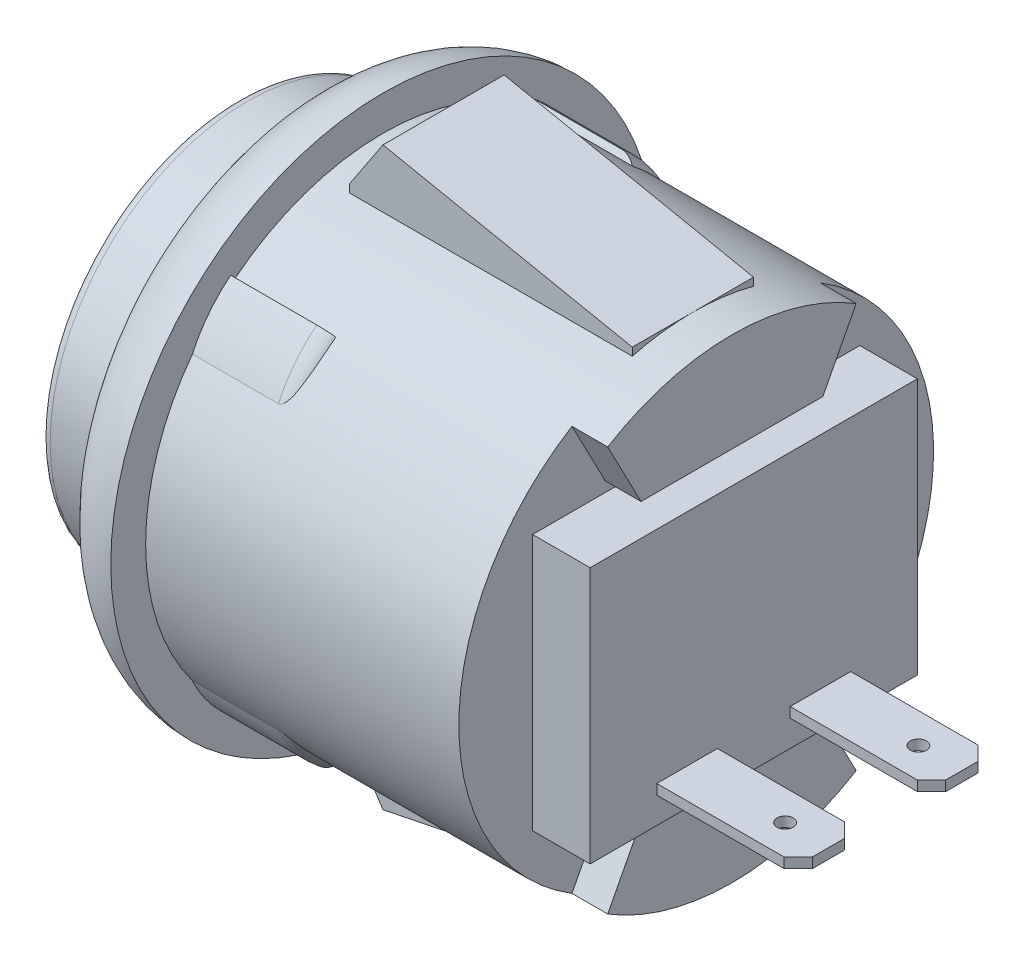
SolidWorks part; units mm, degrees
ref_plane "Front Plane" through (0, 0, 0) normal (0, 0, 1) x (1, 0, 0)
ref_plane "Top Plane" through (0, 0, 0) normal (0, 1, 0) x (1, 0, 0)
ref_plane "Right Plane" through (0, 0, 0) normal (1, 0, 0) x (0, 0, -1)
sketch "Sketch1" plane through (0, 0, 0) normal (0, 0, 1) x (1, 0, 0)
  line L0 (0, 0) -> (0, 9.75)
  line L1 (0, 9.75) -> (3.5, 9.75)
  line L2 (7.225, 13.475) -> (7.225, 11.75)
  line L3 (7.225, 11.75) -> (24.5, 11.75)
  line L4 (24.5, 11.75) -> (24.5, 0)
  line L5 (24.5, 0) -> (0, 0)
  line L6 (0, 0) -> (-7.0673, 0) construction
  line L7 (3.5, 9.75) -> (3.5, 8.8605) construction
  line L8 (7.225, 13.475) -> (8.6863, 13.475) construction
  arc A0 (7.225, 13.475) -> (3.5, 9.75) centre (7.225, 9.75) ccw
  dimension "D1" = 23.5
  dimension "D2" = 19.5
  dimension "D3" = 24.5
  dimension "D4" = 26.95
  dimension "D5" = 3.5
revolve "Revolve1" add sketch "Sketch1" angle 360 about L5
sketch "Sketch7" plane through (7.225, 0, 0) normal (1, 0, 0) x (0, 0, -1)
  line L0 (-7.3373, 9.1775) -> (-7.5402, 9.4314)
  line L1 (0, 0) -> (7.2137, 0) construction
  line L2 (0, 0) -> (0, 5.1375) construction
  line L3 (-7.3373, -9.1775) -> (-7.5402, -9.4314)
  line L4 (7.3373, -9.1775) -> (7.5402, -9.4314)
  line L5 (7.3373, 9.1775) -> (7.5402, 9.4314)
  circle A0 centre (0, 0) radius 12.075 construction
  circle A1 centre (0, 0) radius 11.75 construction
  arc A2 (-7.5402, 9.4314) -> (-9.4373, 7) centre (-3.3839, 4.2327) ccw
  arc A3 (-7.3373, 9.1775) -> (-9.4373, 7) centre (0, 0) ccw
  arc A4 (-7.5402, -9.4314) -> (-9.4373, -7) centre (-3.3839, -4.2327) cw
  arc A5 (-7.3373, -9.1775) -> (-9.4373, -7) centre (0, 0) cw
  arc A6 (7.3373, -9.1775) -> (9.4373, -7) centre (0, 0) ccw
  arc A7 (7.5402, -9.4314) -> (9.4373, -7) centre (3.3839, -4.2327) ccw
  arc A8 (7.5402, 9.4314) -> (9.4373, 7) centre (3.3839, 4.2327) cw
  arc A9 (7.3373, 9.1775) -> (9.4373, 7) centre (0, 0) cw
  dimension "D1" = 24.15
  dimension "D2" = 3
  dimension "D3" = 7
extrude "Boss-Extrude4" add sketch "Sketch7" along normal blind 5.26
fillet "Fillet2" radius 1 4 edges at (12.485, -8.3271, 8.6315) (12.485, -8.3271, -8.6315) (12.485, 8.3271, -8.6315) (12.485, 8.3271, 8.6315)
sketch "Sketch8" plane through (24.5, 0, 0) normal (1, 0, 0) x (0, 0, -1)
  line L0 (-6.15, 10.012) -> (-4.5, 6.85)
  line L1 (-4.5, 6.85) -> (4.5, 6.85)
  line L2 (4.5, 6.85) -> (6.15, 10.012)
  line L3 (0, 0) -> (9.6231, 0) construction
  line L4 (4.5, -6.85) -> (6.15, -10.012)
  line L5 (-4.5, -6.85) -> (4.5, -6.85)
  line L6 (-6.15, -10.012) -> (-4.5, -6.85)
  circle A0 centre (0, 0) radius 11.75 construction
  arc A1 (7.3373, 9.1775) -> (-7.3373, 9.1775) centre (0, 0) ccw construction
  arc A2 (6.15, 10.012) -> (-6.15, 10.012) centre (0, 0) ccw
  arc A3 (6.15, -10.012) -> (-6.15, -10.012) centre (0, 0) cw
  point P4 (0, 6.85)
  dimension "D1" = 12.3
  dimension "D2" = 9
  dimension "D3" = 6.85
extrude "Cut-Extrude2" cut sketch "Sketch8" against normal blind 1.77 flip side to cut
sketch "Sketch2" plane through (22.73, 0, 0) normal (1, 0, 0) x (0, 0, -1)
  line L1 (-8.1, 6.35) -> (8.1, 6.35)
  line L2 (-8.1, 6.35) -> (-8.1, -6.35)
  line L3 (-8.1, -6.35) -> (8.1, -6.35)
  line L4 (8.1, 6.35) -> (8.1, -6.35)
  line L5 (-8.1, 6.35) -> (8.1, -6.35) construction
  line L6 (-8.1, -6.35) -> (8.1, 6.35) construction
  point P0 (0, 0)
  dimension "D1" = 16.2
  dimension "D2" = 12.7
extrude "Boss-Extrude1" add sketch "Sketch2" along normal blind 2.85
sketch "Sketch3" plane through (25.58, 0, 0) normal (1, 0, 0) x (0, 0, -1)
  line L0 (0, 0) -> (0, -4.1104) construction
  line L1 (-4.8, -5.05) -> (-4.8, -4.55)
  line L2 (-4.8, -5.05) -> (-1.8, -5.05)
  line L3 (-1.8, -5.05) -> (-1.8, -4.55)
  line L4 (-4.8, -4.55) -> (-1.8, -4.55)
  line L5 (1.8, -5.05) -> (1.8, -4.55)
  line L6 (1.8, -5.05) -> (4.8, -5.05)
  line L7 (4.8, -5.05) -> (4.8, -4.55)
  line L8 (1.8, -4.55) -> (4.8, -4.55)
  line L9 (-8.1, -6.35) -> (8.1, -6.35) construction
  dimension "D1" = 0.5
  dimension "D2" = 3
  dimension "D3" = 3.6
  dimension "D4" = 1.3
extrude "Boss-Extrude2" add sketch "Sketch3" along normal blind 7
sketch "Sketch4" plane through (0, -4.55, 0) normal (0, 1, 0) x (-1, 0, 0)
  line L0 (-32.58, 1.8) -> (-32.58, 4.8) construction
  line L1 (-32.58, -4.8) -> (-32.58, -1.8) construction
  circle A0 centre (-30.43, 3.3) radius 0.4
  circle A1 centre (-30.43, -3.3) radius 0.4
  point P8 (-32.58, 3.3)
  point P12 (-32.58, -3.3)
  dimension "D1" = 0.8
  dimension "D2" = 2.15
extrude "Cut-Extrude1" cut sketch "Sketch4" against normal through all
chamfer "Chamfer1" distance 0.7 angle 45 4 edges at (32.58, -4.8, -4.8) (32.58, -4.8, -1.8) (32.58, -4.8, 1.8) (32.58, -4.8, 4.8)
sketch "Sketch5" plane through (0, 0, 0) normal (0, 0, 1) x (1, 0, 0)
  line L0 (22.5667, -11.75) -> (10.225, -14.25)
  line L2 (10.225, -14.25) -> (8.5667, -11.75)
  line L4 (0, 0) -> (-5.0022, 0) construction
  line L5 (8.5667, 10.75) -> (8.5667, 11.75)
  line L6 (22.5667, 10.75) -> (8.5667, 10.75)
  line L7 (22.5667, -11.75) -> (22.5667, -10.75)
  line L8 (22.5667, -10.75) -> (8.5667, -10.75)
  line L9 (8.5667, -10.75) -> (8.5667, -11.75)
  line L10 (7.225, -13.475) -> (7.225, 13.475) construction
  line L11 (22.5667, 11.75) -> (22.5667, 10.75)
  line L12 (10.225, 14.25) -> (8.5667, 11.75)
  line L13 (22.5667, 11.75) -> (10.225, 14.25)
  line L14 (7.225, -11.75) -> (24.5, -11.75)
  line L15 (24.5, 11.75) -> (7.225, 11.75)
  line L17 (7.225, -11.75) -> (24.5, -11.75) construction
  dimension "D1" = 2.5
  dimension "D2" = 14
  dimension "D3" = 3
  dimension "D4" = 3
  dimension "D5" = 1
extrude "Boss-Extrude3" add sketch "Sketch5" along normal mid plane 6
fillet "Fillet1" radius 0.5 1 edges at (0, 0, -9.75)
